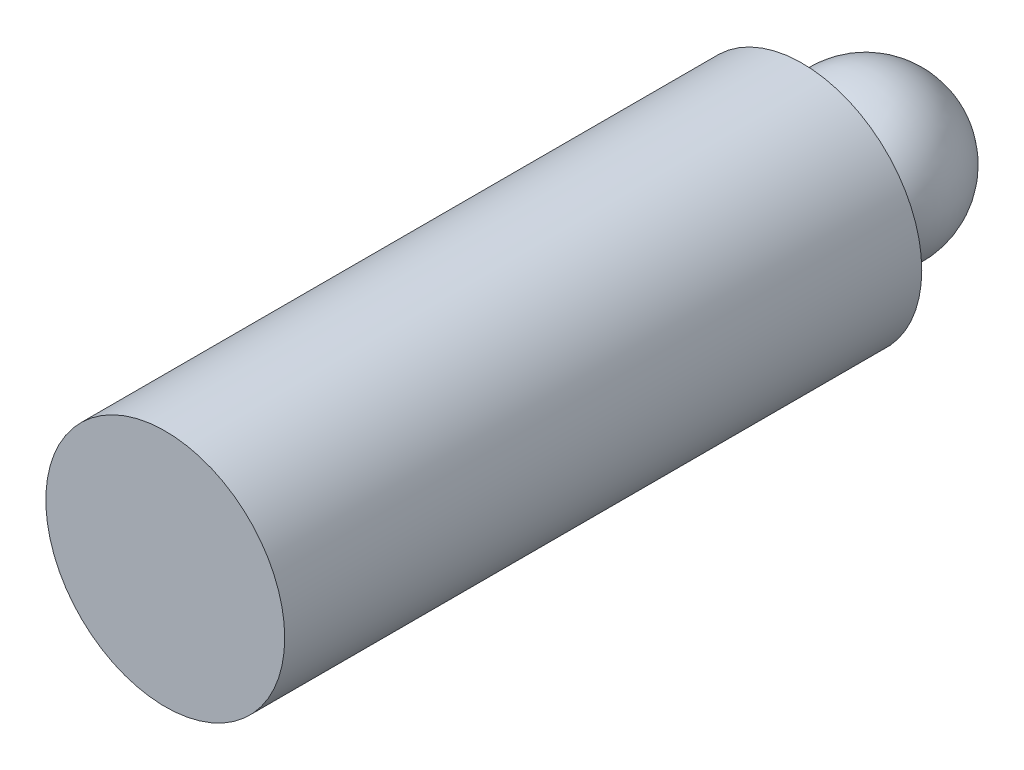
SolidWorks part; units mm, degrees
ref_plane "前视基准面" through (0, 0, 0) normal (0, 0, 1) x (1, 0, 0)
ref_plane "上视基准面" through (0, 0, 0) normal (0, 1, 0) x (1, 0, 0)
ref_plane "右视基准面" through (0, 0, 0) normal (1, 0, 0) x (0, 0, -1)
other "Configuration Table"
sketch "草图1" plane through (0, 0, 0) normal (0, 0, 1) x (1, 0, 0)
  circle A0 centre (0, 0) radius 15
  dimension "D1" = 30
extrude "凸台-拉伸1" add sketch "草图1" along normal blind 80
sketch "草图3" plane through (0, 0, 0) normal (0, 1, 0) x (1, 0, 0)
  line L0 (0, 17.9415) -> (0, -2.0585)
  arc A0 (0, 17.9415) -> (0, -2.0585) centre (0, 7.9415) ccw
  dimension "D1" = 20
revolve "旋转1" add sketch "草图3" angle 360 about L0
sketch "草图4" plane through (0, 0, 0) normal (1, 0, 0) x (0, 0, -1)
  circle A1 centre (7.9415, 0) radius 10 construction
  point P0 (7.9415, 0)
  point P1 (7.9415, 0)
